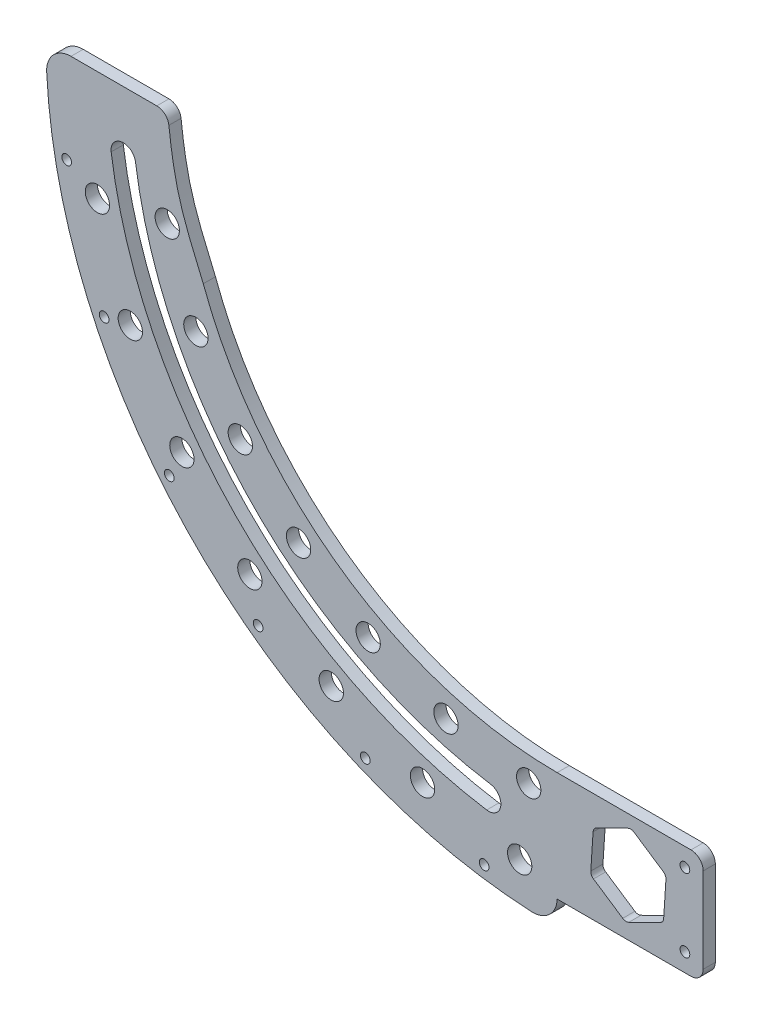
SolidWorks part; units mm, degrees
ref_plane "Front Plane" through (0, 0, 0) normal (0, 0, 1) x (1, 0, 0)
ref_plane "Top Plane" through (0, 0, 0) normal (0, 1, 0) x (1, 0, 0)
ref_plane "Right Plane" through (0, 0, 0) normal (1, 0, 0) x (0, 0, -1)
sketch "Layout" plane through (0, 0, 0) normal (0, 0, 1) x (1, 0, 0)
  line L0 (0, 0) -> (-76.2, 0) construction
  line L1 (-76.2, 0) -> (-203.2, 0) construction
  line L2 (-203.2, 0) -> (-254, 0) construction
  dimension "D1" = 76.2
  dimension "D2" = 127
  dimension "D3" = 50.8
sketch "Sketch1" plane through (0, 0, 0) normal (0, 0, 1) x (1, 0, 0)
  line L0 (0, 0) -> (-203.2, 0) construction
  line L1 (0, 0) -> (0, -203.2) construction
  line L2 (0, -203.2) -> (76.2, -203.2)
  line L3 (0, -254) -> (76.2, -254)
  line L4 (-254, 0) -> (-203.2, 0)
  line L5 (76.2, -203.2) -> (76.2, -254)
  arc A0 (-203.2, 0) -> (0, -203.2) centre (0, 0) ccw
  arc A1 (-254, 0) -> (0, -254) centre (0, 0) ccw
  dimension "D1" = 50.8
  dimension "D2" = 76.2
  dimension "D3" = 203.2
extrude "Boss-Extrude1" add sketch "Sketch1" along normal blind 6.35
ref_plane "Mid_Plane" through (0, 0, 3.175) normal (0, 0, 1) x (1, 0, 0)
sketch "Sketch2" plane through (0, 0, 6.35) normal (0, 0, 1) x (1, 0, 0)
  line L0 (0, 0) -> (-229.3095, 0) construction
  line L1 (0, 0) -> (-226.3753, -31.815) construction
  line L2 (0, 0) -> (-35.7609, -225.7856) construction
  arc A0 (-226.3753, -31.815) -> (-35.7609, -225.7856) centre (0, 0) ccw construction
  arc A1 (-226.3753, -31.815) -> (-35.7609, -225.7856) centre (0, 0) ccw construction
  arc A2 (-232.7264, -32.7076) -> (-36.7642, -232.1201) centre (0, 0) ccw
  arc A3 (-220.0242, -30.9224) -> (-34.7576, -219.451) centre (0, 0) ccw
  arc A4 (-220.0242, -30.9224) -> (-232.7264, -32.7076) centre (-226.3753, -31.815) ccw
  arc A5 (-36.7642, -232.1201) -> (-34.7576, -219.451) centre (-35.7609, -225.7856) ccw
  point P5 (-163.0491, -160.2279)
  dimension "D1" = 73
  dimension "D3" = 12.827
  dimension "D4" = 228.6
  dimension "D2" = 8
extrude "Cut-Extrude1" cut sketch "Sketch2" against normal up to next
fillet "Fillet1" [suppressed] radius 12.7
ref_point "Mid_Point"
sketch "Sketch4" plane through (0, 0, 0) normal (0, 0, -1) x (-1, 0, 0)
  line L0 (254, 0) -> (266.7, 0)
  line L1 (0, -254) -> (0, -266.7)
  arc A0 (0, -254) -> (254, 0) centre (0, 0) ccw construction
  arc A1 (0, -254) -> (254, 0) centre (0, 0) ccw
  arc A2 (0, -266.7) -> (266.7, 0) centre (0, 0) ccw
extrude "Boss-Extrude3" add sketch "Sketch4" against normal up to surface (6.35 mm away) up to face at (-145.6981, -143.1771, 6.35)
fillet "Fillet2" radius 12.7 2 edges at (-266.7, 0, 3.175) (0, -266.7, 3.175)
sketch "Sketch5" plane through (0, 0, 0) normal (0, 0, -1) x (-1, 0, 0)
  line L0 (2.758, -261.6055) -> (3.6103, -266.6756)
  line L1 (0, 0) -> (306.4939, -16.1536) construction
  line L2 (0, -261.62) -> (0.7987, -266.6988)
  line L3 (0, -261.62) -> (-1.3603, -266.6965)
  line L4 (2.758, -261.6055) -> (1.4514, -266.6961)
  line L5 (5.5157, -261.5618) -> (6.4214, -266.6227)
  line L6 (5.5157, -261.5618) -> (4.2628, -266.6659)
  line L7 (8.2728, -261.4892) -> (9.2318, -266.5402)
  line L8 (8.2728, -261.4892) -> (7.0738, -266.6062)
  line L9 (11.029, -261.3874) -> (12.0411, -266.428)
  line L10 (11.029, -261.3874) -> (9.884, -266.5168)
  line L11 (13.7839, -261.2566) -> (14.8492, -266.2863)
  line L12 (13.7839, -261.2566) -> (12.693, -266.3978)
  line L13 (16.5374, -261.0968) -> (17.6555, -266.115)
  line L14 (16.5374, -261.0968) -> (15.5007, -266.2492)
  line L15 (19.2889, -260.908) -> (20.46, -265.914)
  line L16 (19.2889, -260.908) -> (18.3067, -266.071)
  line L17 (22.0384, -260.6901) -> (23.2621, -265.6836)
  line L18 (22.0384, -260.6901) -> (21.1106, -265.8632)
  line L19 (24.7854, -260.4433) -> (26.0617, -265.4236)
  line L20 (24.7854, -260.4433) -> (23.9122, -265.6259)
  line L21 (27.5296, -260.1675) -> (28.8583, -265.1341)
  line L22 (27.5296, -260.1675) -> (26.7111, -265.359)
  line L23 (30.2708, -259.8629) -> (31.6518, -264.8151)
  line L24 (30.2708, -259.8629) -> (29.507, -265.0627)
  line L25 (33.0086, -259.5293) -> (34.4417, -264.4667)
  line L26 (33.0086, -259.5293) -> (32.2997, -264.7369)
  line L27 (35.7427, -259.1669) -> (37.2278, -264.089)
  line L28 (35.7427, -259.1669) -> (35.0888, -264.3817)
  line L29 (38.4729, -258.7757) -> (40.0098, -263.6818)
  line L30 (38.4729, -258.7757) -> (37.874, -263.9971)
  line L31 (41.1988, -258.3557) -> (42.7873, -263.2454)
  line L32 (41.1988, -258.3557) -> (40.6549, -263.5831)
  line L33 (43.9201, -257.9071) -> (45.5601, -262.7797)
  line L34 (43.9201, -257.9071) -> (43.4314, -263.1399)
  line L35 (46.6365, -257.4297) -> (48.3278, -262.2848)
  line L36 (46.6365, -257.4297) -> (46.203, -262.6674)
  line L37 (49.3478, -256.9238) -> (51.0902, -261.7607)
  line L38 (49.3478, -256.9238) -> (48.9695, -262.1657)
  line L39 (52.0535, -256.3893) -> (53.8468, -261.2076)
  line L40 (52.0535, -256.3893) -> (51.7305, -261.6349)
  line L41 (54.7535, -255.8263) -> (56.5975, -260.6254)
  line L42 (54.7535, -255.8263) -> (54.4858, -261.0751)
  line L43 (57.4474, -255.2348) -> (59.3419, -260.0143)
  line L44 (57.4474, -255.2348) -> (57.2351, -260.4862)
  line L45 (60.1349, -254.615) -> (62.0797, -259.3743)
  line L46 (60.1349, -254.615) -> (59.978, -259.8683)
  line L47 (62.8157, -253.9669) -> (64.8106, -258.7054)
  line L48 (62.8157, -253.9669) -> (62.7142, -259.2216)
  line L49 (65.4896, -253.2906) -> (67.5342, -258.0078)
  line L50 (65.4896, -253.2906) -> (65.4434, -258.546)
  line L51 (68.1561, -252.5862) -> (70.2504, -257.2815)
  line L52 (68.1561, -252.5862) -> (68.1654, -257.8418)
  line L53 (70.8151, -251.8536) -> (72.9588, -256.5266)
  line L54 (70.8151, -251.8536) -> (70.8798, -257.1088)
  line L55 (73.4663, -251.0931) -> (75.6591, -255.7432)
  line L56 (73.4663, -251.0931) -> (73.5863, -256.3473)
  line L57 (76.1092, -250.3046) -> (78.3509, -254.9314)
  line L58 (76.1092, -250.3046) -> (76.2846, -255.5573)
  line L59 (78.7437, -249.4884) -> (81.0341, -254.0913)
  line L60 (78.7437, -249.4884) -> (78.9745, -254.7389)
  line L61 (81.3695, -248.6444) -> (83.7082, -253.2229)
  line L62 (81.3695, -248.6444) -> (81.6556, -253.8922)
  line L63 (83.9862, -247.7728) -> (86.373, -252.3263)
  line L64 (83.9862, -247.7728) -> (84.3276, -253.0173)
  line L65 (86.5935, -246.8736) -> (89.0283, -251.4018)
  line L66 (86.5935, -246.8736) -> (86.9902, -252.1142)
  line L67 (89.1913, -245.947) -> (91.6736, -250.4493)
  line L68 (89.1913, -245.947) -> (89.6432, -251.1832)
  line L69 (91.7791, -244.9931) -> (94.3088, -249.4689)
  line L70 (91.7791, -244.9931) -> (92.2862, -250.2242)
  line L71 (94.3567, -244.0119) -> (96.9335, -248.4608)
  line L72 (94.3567, -244.0119) -> (94.919, -249.2374)
  line L73 (96.9239, -243.0037) -> (99.5474, -247.4252)
  line L74 (96.9239, -243.0037) -> (97.5412, -248.2229)
  line L75 (99.4803, -241.9684) -> (102.1502, -246.362)
  line L76 (99.4803, -241.9684) -> (100.1525, -247.1808)
  line L77 (102.0256, -240.9062) -> (104.7417, -245.2714)
  line L78 (102.0256, -240.9062) -> (102.7528, -246.1113)
  line L79 (104.5596, -239.8173) -> (107.3215, -244.1536)
  line L80 (104.5596, -239.8173) -> (105.3416, -245.0144)
  line L81 (107.0819, -238.7017) -> (109.8895, -243.0086)
  line L82 (107.0819, -238.7017) -> (107.9187, -243.8902)
  line L83 (109.5924, -237.5595) -> (112.4452, -241.8367)
  line L84 (109.5924, -237.5595) -> (110.4838, -242.739)
  line L85 (112.0907, -236.391) -> (114.9884, -240.6378)
  line L86 (112.0907, -236.391) -> (113.0366, -241.5608)
  line L87 (114.5765, -235.1962) -> (117.5188, -239.4122)
  line L88 (114.5765, -235.1962) -> (115.5769, -240.3557)
  line L89 (117.0496, -233.9753) -> (120.0362, -238.16)
  line L90 (117.0496, -233.9753) -> (118.1043, -239.124)
  line L91 (119.5096, -232.7283) -> (122.5402, -236.8814)
  line L92 (119.5096, -232.7283) -> (120.6186, -237.8656)
  line L93 (121.9564, -231.4555) -> (125.0306, -235.5764)
  line L94 (121.9564, -231.4555) -> (123.1195, -236.5808)
  line L95 (124.3897, -230.157) -> (127.5071, -234.2452)
  line L96 (124.3897, -230.157) -> (125.6067, -235.2697)
  line L97 (126.8091, -228.8329) -> (129.9695, -232.888)
  line L98 (126.8091, -228.8329) -> (128.0799, -233.9325)
  line L99 (129.2144, -227.4833) -> (132.4174, -231.5049)
  line L100 (129.2144, -227.4833) -> (130.539, -232.5693)
  line L101 (131.6054, -226.1085) -> (134.8505, -230.0961)
  line L102 (131.6054, -226.1085) -> (132.9835, -231.1802)
  line L103 (133.9817, -224.7085) -> (137.2687, -228.6617)
  line L104 (133.9817, -224.7085) -> (135.4132, -229.7654)
  line L105 (136.3432, -223.2836) -> (139.6717, -227.2019)
  line L106 (136.3432, -223.2836) -> (137.8279, -228.3251)
  line L107 (138.6895, -221.8339) -> (142.0591, -225.7169)
  line L108 (138.6895, -221.8339) -> (140.2272, -226.8595)
  line L109 (141.0203, -220.3595) -> (144.4307, -224.2067)
  line L110 (141.0203, -220.3595) -> (142.611, -225.3686)
  line L111 (143.3355, -218.8606) -> (146.7863, -222.6717)
  line L112 (143.3355, -218.8606) -> (144.9789, -223.8526)
  line L113 (145.6348, -217.3374) -> (149.1256, -221.1119)
  line L114 (145.6348, -217.3374) -> (147.3307, -222.3118)
  line L115 (147.9179, -215.79) -> (151.4482, -219.5275)
  line L116 (147.9179, -215.79) -> (149.6662, -220.7463)
  line L117 (150.1846, -214.2186) -> (153.7541, -217.9187)
  line L118 (150.1846, -214.2186) -> (151.985, -219.1562)
  line L119 (152.4345, -212.6235) -> (156.0429, -216.2857)
  line L120 (152.4345, -212.6235) -> (154.2869, -217.5418)
  line L121 (154.6675, -211.0047) -> (158.3143, -214.6287)
  line L122 (154.6675, -211.0047) -> (156.5717, -215.9032)
  line L123 (156.8834, -209.3624) -> (160.5681, -212.9478)
  line L124 (156.8834, -209.3624) -> (158.839, -214.2407)
  line L125 (159.0818, -207.6969) -> (162.8041, -211.2432)
  line L126 (159.0818, -207.6969) -> (161.0887, -212.5543)
  line L127 (161.2625, -206.0083) -> (165.022, -209.5152)
  line L128 (161.2625, -206.0083) -> (163.3205, -210.8442)
  line L129 (163.4253, -204.2969) -> (167.2216, -207.7639)
  line L130 (163.4253, -204.2969) -> (165.5342, -209.1108)
  line L131 (165.5699, -202.5627) -> (169.4025, -205.9895)
  line L132 (165.5699, -202.5627) -> (167.7295, -207.3541)
  line L133 (167.6961, -200.806) -> (171.5647, -204.1922)
  line L134 (167.6961, -200.806) -> (169.9061, -205.5744)
  line L135 (169.8037, -199.0269) -> (173.7077, -202.3722)
  line L136 (169.8037, -199.0269) -> (172.0638, -203.7718)
  line L137 (171.8924, -197.2258) -> (175.8315, -200.5297)
  line L138 (171.8924, -197.2258) -> (174.2024, -201.9465)
  line L139 (173.962, -195.4027) -> (177.9357, -198.665)
  line L140 (173.962, -195.4027) -> (176.3217, -200.0989)
  line L141 (176.0123, -193.558) -> (180.0202, -196.7781)
  line L142 (176.0123, -193.558) -> (178.4213, -198.229)
  line L143 (178.043, -191.6917) -> (182.0846, -194.8694)
  line L144 (178.043, -191.6917) -> (180.5012, -196.337)
  line L145 (180.054, -189.8041) -> (184.1288, -192.939)
  line L146 (180.054, -189.8041) -> (182.5609, -194.4232)
  line L147 (182.0449, -187.8954) -> (186.1526, -190.9872)
  line L148 (182.0449, -187.8954) -> (184.6004, -192.4879)
  line L149 (184.0156, -185.9658) -> (188.1556, -189.0141)
  line L150 (184.0156, -185.9658) -> (186.6194, -190.5311)
  line L151 (185.9658, -184.0156) -> (190.1378, -187.0201)
  line L152 (185.9658, -184.0156) -> (188.6176, -188.5532)
  line L153 (187.8954, -182.0449) -> (192.0988, -185.0053)
  line L154 (187.8954, -182.0449) -> (190.5948, -186.5543)
  line L155 (189.8041, -180.054) -> (194.0384, -182.9699)
  line L156 (189.8041, -180.054) -> (192.5509, -184.5346)
  line L157 (191.6917, -178.043) -> (195.9565, -180.9141)
  line L158 (191.6917, -178.043) -> (194.4856, -182.4945)
  line L159 (193.558, -176.0123) -> (197.8529, -178.8383)
  line L160 (193.558, -176.0123) -> (196.3987, -180.4341)
  line L161 (195.4027, -173.962) -> (199.7272, -176.7426)
  line L162 (195.4027, -173.962) -> (198.2899, -178.3536)
  line L163 (197.2258, -171.8924) -> (201.5793, -174.6272)
  line L164 (197.2258, -171.8924) -> (200.1591, -176.2533)
  line L165 (199.0269, -169.8037) -> (203.4091, -172.4925)
  line L166 (199.0269, -169.8037) -> (202.006, -174.1334)
  line L167 (200.806, -167.6961) -> (205.2162, -170.3385)
  line L168 (200.806, -167.6961) -> (203.8305, -171.9942)
  line L169 (202.5627, -165.5699) -> (207.0005, -168.1656)
  line L170 (202.5627, -165.5699) -> (205.6324, -169.8358)
  line L171 (204.2969, -163.4253) -> (208.7618, -165.9741)
  line L172 (204.2969, -163.4253) -> (207.4114, -167.6586)
  line L173 (206.0083, -161.2625) -> (210.4999, -163.7641)
  line L174 (206.0083, -161.2625) -> (209.1673, -165.4628)
  line L175 (207.6969, -159.0818) -> (212.2146, -161.5359)
  line L176 (207.6969, -159.0818) -> (210.9, -163.2485)
  line L177 (209.3624, -156.8834) -> (213.9058, -159.2897)
  line L178 (209.3624, -156.8834) -> (212.6093, -161.0161)
  line L179 (211.0047, -154.6675) -> (215.5731, -157.0259)
  line L180 (211.0047, -154.6675) -> (214.2949, -158.7658)
  line L181 (212.6235, -152.4345) -> (217.2165, -154.7446)
  line L182 (212.6235, -152.4345) -> (215.9567, -156.4979)
  line L183 (214.2186, -150.1846) -> (218.8358, -152.446)
  line L184 (214.2186, -150.1846) -> (217.5945, -154.2126)
  line L185 (215.79, -147.9179) -> (220.4307, -150.1306)
  line L186 (215.79, -147.9179) -> (219.2081, -151.9101)
  line L187 (217.3374, -145.6348) -> (222.0011, -147.7985)
  line L188 (217.3374, -145.6348) -> (220.7974, -149.5908)
  line L189 (218.8606, -143.3355) -> (223.5469, -145.4499)
  line L190 (218.8606, -143.3355) -> (222.3621, -147.2548)
  line L191 (220.3595, -141.0203) -> (225.0678, -143.0852)
  line L192 (220.3595, -141.0203) -> (223.9021, -144.9024)
  line L193 (221.8339, -138.6895) -> (226.5637, -140.7045)
  line L194 (221.8339, -138.6895) -> (225.4173, -142.534)
  line L195 (223.2836, -136.3432) -> (228.0345, -138.3083)
  line L196 (223.2836, -136.3432) -> (226.9074, -140.1497)
  line L197 (224.7085, -133.9817) -> (229.4798, -135.8966)
  line L198 (224.7085, -133.9817) -> (228.3722, -137.7499)
  line L199 (226.1085, -131.6054) -> (230.8997, -133.4699)
  line L200 (226.1085, -131.6054) -> (229.8117, -135.3347)
  line L201 (227.4833, -129.2144) -> (232.2939, -131.0283)
  line L202 (227.4833, -129.2144) -> (231.2256, -132.9045)
  line L203 (228.8329, -126.8091) -> (233.6623, -128.5722)
  line L204 (228.8329, -126.8091) -> (232.6139, -130.4595)
  line L205 (230.157, -124.3897) -> (235.0048, -126.1017)
  line L206 (230.157, -124.3897) -> (233.9762, -128)
  line L207 (231.4555, -121.9564) -> (236.3211, -123.6173)
  line L208 (231.4555, -121.9564) -> (235.3126, -125.5263)
  line L209 (232.7283, -119.5096) -> (237.6111, -121.1191)
  line L210 (232.7283, -119.5096) -> (236.6229, -123.0387)
  line L211 (233.9753, -117.0496) -> (238.8748, -118.6075)
  line L212 (233.9753, -117.0496) -> (237.9068, -120.5373)
  line L213 (235.1962, -114.5765) -> (240.1119, -116.0827)
  line L214 (235.1962, -114.5765) -> (239.1643, -118.0226)
  line L215 (236.391, -112.0907) -> (241.3223, -113.5449)
  line L216 (236.391, -112.0907) -> (240.3952, -115.4948)
  line L217 (237.5595, -109.5924) -> (242.5059, -110.9946)
  line L218 (237.5595, -109.5924) -> (241.5994, -112.9541)
  line L219 (238.7017, -107.0819) -> (243.6625, -108.4319)
  line L220 (238.7017, -107.0819) -> (242.7767, -110.4009)
  line L221 (239.8173, -104.5596) -> (244.792, -105.8572)
  line L222 (239.8173, -104.5596) -> (243.9271, -107.8353)
  line L223 (240.9062, -102.0256) -> (245.8944, -103.2707)
  line L224 (240.9062, -102.0256) -> (245.0503, -105.2579)
  line L225 (241.9684, -99.4803) -> (246.9694, -100.6727)
  line L226 (241.9684, -99.4803) -> (246.1464, -102.6687)
  line L227 (243.0037, -96.9239) -> (248.017, -98.0636)
  line L228 (243.0037, -96.9239) -> (247.215, -100.0681)
  line L229 (244.0119, -94.3567) -> (249.037, -95.4435)
  line L230 (244.0119, -94.3567) -> (248.2562, -97.4564)
  line L231 (244.9931, -91.7791) -> (250.0293, -92.8128)
  line L232 (244.9931, -91.7791) -> (249.2698, -94.8338)
  line L233 (245.947, -89.1913) -> (250.9939, -90.1718)
  line L234 (245.947, -89.1913) -> (250.2557, -92.2007)
  line L235 (246.8736, -86.5935) -> (251.9305, -87.5208)
  line L236 (246.8736, -86.5935) -> (251.2138, -89.5574)
  line L237 (247.7728, -83.9862) -> (252.8392, -84.8601)
  line L238 (247.7728, -83.9862) -> (252.1439, -86.9041)
  line L239 (248.6444, -81.3695) -> (253.7197, -82.1899)
  line L240 (248.6444, -81.3695) -> (253.0461, -84.2412)
  line L241 (249.4884, -78.7437) -> (254.5721, -79.5107)
  line L242 (249.4884, -78.7437) -> (253.9201, -81.5689)
  line L243 (250.3046, -76.1092) -> (255.3961, -76.8225)
  line L244 (250.3046, -76.1092) -> (254.7659, -78.8875)
  line L245 (251.0931, -73.4663) -> (256.1918, -74.1258)
  line L246 (251.0931, -73.4663) -> (255.5834, -76.1973)
  line L247 (251.8536, -70.8151) -> (256.959, -71.4209)
  line L248 (251.8536, -70.8151) -> (256.3724, -73.4987)
  line L249 (252.5862, -68.1561) -> (257.6977, -68.7081)
  line L250 (252.5862, -68.1561) -> (257.133, -70.7919)
  line L251 (253.2906, -65.4896) -> (258.4077, -65.9876)
  line L252 (253.2906, -65.4896) -> (257.865, -68.0773)
  line L253 (253.9669, -62.8157) -> (259.089, -63.2598)
  line L254 (253.9669, -62.8157) -> (258.5684, -65.3551)
  line L255 (254.615, -60.1349) -> (259.7415, -60.5249)
  line L256 (254.615, -60.1349) -> (259.243, -62.6256)
  line L257 (255.2348, -57.4474) -> (260.3651, -57.7834)
  line L258 (255.2348, -57.4474) -> (259.8888, -59.8892)
  line L259 (255.8263, -54.7535) -> (260.9598, -55.0354)
  line L260 (255.8263, -54.7535) -> (260.5057, -57.1461)
  line L261 (256.3893, -52.0535) -> (261.5254, -52.2813)
  line L262 (256.3893, -52.0535) -> (261.0937, -54.3966)
  line L263 (256.9238, -49.3478) -> (262.0621, -49.5213)
  line L264 (256.9238, -49.3478) -> (261.6526, -51.6412)
  line L265 (257.4297, -46.6365) -> (262.5696, -46.7559)
  line L266 (257.4297, -46.6365) -> (262.1825, -48.8799)
  line L267 (257.9071, -43.9201) -> (263.0479, -43.9853)
  line L268 (257.9071, -43.9201) -> (262.6832, -46.1133)
  line L269 (258.3557, -41.1988) -> (263.497, -41.2098)
  line L270 (258.3557, -41.1988) -> (263.1547, -43.3415)
  line L271 (258.7757, -38.4729) -> (263.9167, -38.4297)
  line L272 (258.7757, -38.4729) -> (263.597, -40.5649)
  line L273 (259.1669, -35.7427) -> (264.3072, -35.6453)
  line L274 (259.1669, -35.7427) -> (264.01, -37.7838)
  line L275 (259.5293, -33.0086) -> (264.6683, -32.857)
  line L276 (259.5293, -33.0086) -> (264.3936, -34.9985)
  line L277 (259.8629, -30.2708) -> (265, -30.065)
  line L278 (259.8629, -30.2708) -> (264.7479, -32.2093)
  line L279 (260.1675, -27.5296) -> (265.3022, -27.2697)
  line L280 (260.1675, -27.5296) -> (265.0727, -29.4165)
  line L281 (260.4433, -24.7854) -> (265.5749, -24.4714)
  line L282 (260.4433, -24.7854) -> (265.3681, -26.6204)
  line L283 (260.6901, -22.0384) -> (265.8181, -21.6703)
  line L284 (260.6901, -22.0384) -> (265.634, -23.8214)
  line L285 (260.908, -19.2889) -> (266.0318, -18.8668)
  line L286 (260.908, -19.2889) -> (265.8704, -21.0198)
  line L287 (261.0968, -16.5374) -> (266.2159, -16.0612)
  line L288 (261.0968, -16.5374) -> (266.0772, -18.2158)
  line L289 (261.2566, -13.7839) -> (266.3705, -13.2539)
  line L290 (261.2566, -13.7839) -> (266.2544, -15.4098)
  line L291 (261.3874, -11.029) -> (266.4954, -10.4451)
  line L292 (261.3874, -11.029) -> (266.4021, -12.602)
  line L301 (0, 0) -> (0, -261.62) construction
  arc A0 (13.3308, -266.3666) -> (266.3664, -13.335) centre (0, 0) ccw construction
  arc A1 (-1.3603, -266.6965) -> (0.7987, -266.6988) centre (0, 0) ccw
  arc A2 (1.4514, -266.6961) -> (3.6103, -266.6756) centre (0, 0) ccw
  arc A3 (4.2628, -266.6659) -> (6.4214, -266.6227) centre (0, 0) ccw
  arc A4 (7.0738, -266.6062) -> (9.2318, -266.5402) centre (0, 0) ccw
  arc A5 (9.884, -266.5168) -> (12.0411, -266.428) centre (0, 0) ccw
  arc A6 (12.693, -266.3978) -> (14.8492, -266.2863) centre (0, 0) ccw
  arc A7 (15.5007, -266.2492) -> (17.6555, -266.115) centre (0, 0) ccw
  arc A8 (18.3067, -266.071) -> (20.46, -265.914) centre (0, 0) ccw
  arc A9 (21.1106, -265.8632) -> (23.2621, -265.6836) centre (0, 0) ccw
  arc A10 (23.9122, -265.6259) -> (26.0617, -265.4236) centre (0, 0) ccw
  arc A11 (26.7111, -265.359) -> (28.8583, -265.1341) centre (0, 0) ccw
  arc A12 (29.507, -265.0627) -> (31.6518, -264.8151) centre (0, 0) ccw
  arc A13 (32.2997, -264.7369) -> (34.4417, -264.4667) centre (0, 0) ccw
  arc A14 (35.0888, -264.3817) -> (37.2278, -264.089) centre (0, 0) ccw
  arc A15 (37.874, -263.9971) -> (40.0098, -263.6818) centre (0, 0) ccw
  arc A16 (40.6549, -263.5831) -> (42.7873, -263.2454) centre (0, 0) ccw
  arc A17 (43.4314, -263.1399) -> (45.5601, -262.7797) centre (0, 0) ccw
  arc A18 (46.203, -262.6674) -> (48.3278, -262.2848) centre (0, 0) ccw
  arc A19 (48.9695, -262.1657) -> (51.0902, -261.7607) centre (0, 0) ccw
  arc A20 (51.7305, -261.6349) -> (53.8468, -261.2076) centre (0, 0) ccw
  arc A21 (54.4858, -261.0751) -> (56.5975, -260.6254) centre (0, 0) ccw
  arc A22 (57.2351, -260.4862) -> (59.3419, -260.0143) centre (0, 0) ccw
  arc A23 (59.978, -259.8683) -> (62.0797, -259.3743) centre (0, 0) ccw
  arc A24 (62.7142, -259.2216) -> (64.8106, -258.7054) centre (0, 0) ccw
  arc A25 (65.4434, -258.546) -> (67.5342, -258.0078) centre (0, 0) ccw
  arc A26 (68.1654, -257.8418) -> (70.2504, -257.2815) centre (0, 0) ccw
  arc A27 (70.8798, -257.1088) -> (72.9588, -256.5266) centre (0, 0) ccw
  arc A28 (73.5863, -256.3473) -> (75.6591, -255.7432) centre (0, 0) ccw
  arc A29 (76.2846, -255.5573) -> (78.3509, -254.9314) centre (0, 0) ccw
  arc A30 (78.9745, -254.7389) -> (81.0341, -254.0913) centre (0, 0) ccw
  arc A31 (81.6556, -253.8922) -> (83.7082, -253.2229) centre (0, 0) ccw
  arc A32 (84.3276, -253.0173) -> (86.373, -252.3263) centre (0, 0) ccw
  arc A33 (86.9902, -252.1142) -> (89.0283, -251.4018) centre (0, 0) ccw
  arc A34 (89.6432, -251.1832) -> (91.6736, -250.4493) centre (0, 0) ccw
  arc A35 (92.2862, -250.2242) -> (94.3088, -249.4689) centre (0, 0) ccw
  arc A36 (94.919, -249.2374) -> (96.9335, -248.4608) centre (0, 0) ccw
  arc A37 (97.5412, -248.2229) -> (99.5474, -247.4252) centre (0, 0) ccw
  arc A38 (100.1525, -247.1808) -> (102.1502, -246.362) centre (0, 0) ccw
  arc A39 (102.7528, -246.1113) -> (104.7417, -245.2714) centre (0, 0) ccw
  arc A40 (105.3416, -245.0144) -> (107.3215, -244.1536) centre (0, 0) ccw
  arc A41 (107.9187, -243.8902) -> (109.8895, -243.0086) centre (0, 0) ccw
  arc A42 (110.4838, -242.739) -> (112.4452, -241.8367) centre (0, 0) ccw
  arc A43 (113.0366, -241.5608) -> (114.9884, -240.6378) centre (0, 0) ccw
  arc A44 (115.5769, -240.3557) -> (117.5188, -239.4122) centre (0, 0) ccw
  arc A45 (118.1043, -239.124) -> (120.0362, -238.16) centre (0, 0) ccw
  arc A46 (120.6186, -237.8656) -> (122.5402, -236.8814) centre (0, 0) ccw
  arc A47 (123.1195, -236.5808) -> (125.0306, -235.5764) centre (0, 0) ccw
  arc A48 (125.6067, -235.2697) -> (127.5071, -234.2452) centre (0, 0) ccw
  arc A49 (128.0799, -233.9325) -> (129.9695, -232.888) centre (0, 0) ccw
  arc A50 (130.539, -232.5693) -> (132.4174, -231.5049) centre (0, 0) ccw
  arc A51 (132.9835, -231.1802) -> (134.8505, -230.0961) centre (0, 0) ccw
  arc A52 (135.4132, -229.7654) -> (137.2687, -228.6617) centre (0, 0) ccw
  arc A53 (137.8279, -228.3251) -> (139.6717, -227.2019) centre (0, 0) ccw
  arc A54 (140.2272, -226.8595) -> (142.0591, -225.7169) centre (0, 0) ccw
  arc A55 (142.611, -225.3686) -> (144.4307, -224.2067) centre (0, 0) ccw
  arc A56 (144.9789, -223.8526) -> (146.7863, -222.6717) centre (0, 0) ccw
  arc A57 (147.3307, -222.3118) -> (149.1256, -221.1119) centre (0, 0) ccw
  arc A58 (149.6662, -220.7463) -> (151.4482, -219.5275) centre (0, 0) ccw
  arc A59 (151.985, -219.1562) -> (153.7541, -217.9187) centre (0, 0) ccw
  arc A60 (154.2869, -217.5418) -> (156.0429, -216.2857) centre (0, 0) ccw
  arc A61 (156.5717, -215.9032) -> (158.3143, -214.6287) centre (0, 0) ccw
  arc A62 (158.839, -214.2407) -> (160.5681, -212.9478) centre (0, 0) ccw
  arc A63 (161.0887, -212.5543) -> (162.8041, -211.2432) centre (0, 0) ccw
  arc A64 (163.3205, -210.8442) -> (165.022, -209.5152) centre (0, 0) ccw
  arc A65 (165.5342, -209.1108) -> (167.2216, -207.7639) centre (0, 0) ccw
  arc A66 (167.7295, -207.3541) -> (169.4025, -205.9895) centre (0, 0) ccw
  arc A67 (169.9061, -205.5744) -> (171.5647, -204.1922) centre (0, 0) ccw
  arc A68 (172.0638, -203.7718) -> (173.7077, -202.3722) centre (0, 0) ccw
  arc A69 (174.2024, -201.9465) -> (175.8315, -200.5297) centre (0, 0) ccw
  arc A70 (176.3217, -200.0989) -> (177.9357, -198.665) centre (0, 0) ccw
  arc A71 (178.4213, -198.229) -> (180.0202, -196.7781) centre (0, 0) ccw
  arc A72 (180.5012, -196.337) -> (182.0846, -194.8694) centre (0, 0) ccw
  arc A73 (182.5609, -194.4232) -> (184.1288, -192.939) centre (0, 0) ccw
  arc A74 (184.6004, -192.4879) -> (186.1526, -190.9872) centre (0, 0) ccw
  arc A75 (186.6194, -190.5311) -> (188.1556, -189.0141) centre (0, 0) ccw
  arc A76 (188.6176, -188.5532) -> (190.1378, -187.0201) centre (0, 0) ccw
  arc A77 (190.5948, -186.5543) -> (192.0988, -185.0053) centre (0, 0) ccw
  arc A78 (192.5509, -184.5346) -> (194.0384, -182.9699) centre (0, 0) ccw
  arc A79 (194.4856, -182.4945) -> (195.9565, -180.9141) centre (0, 0) ccw
  arc A80 (196.3987, -180.4341) -> (197.8529, -178.8383) centre (0, 0) ccw
  arc A81 (198.2899, -178.3536) -> (199.7272, -176.7426) centre (0, 0) ccw
  arc A82 (200.1591, -176.2533) -> (201.5793, -174.6272) centre (0, 0) ccw
  arc A83 (202.006, -174.1334) -> (203.4091, -172.4925) centre (0, 0) ccw
  arc A84 (203.8305, -171.9942) -> (205.2162, -170.3385) centre (0, 0) ccw
  arc A85 (205.6324, -169.8358) -> (207.0005, -168.1656) centre (0, 0) ccw
  arc A86 (207.4114, -167.6586) -> (208.7618, -165.9741) centre (0, 0) ccw
  arc A87 (209.1673, -165.4628) -> (210.4999, -163.7641) centre (0, 0) ccw
  arc A88 (210.9, -163.2485) -> (212.2146, -161.5359) centre (0, 0) ccw
  arc A89 (212.6093, -161.0161) -> (213.9058, -159.2897) centre (0, 0) ccw
  arc A90 (214.2949, -158.7658) -> (215.5731, -157.0259) centre (0, 0) ccw
  arc A91 (215.9567, -156.4979) -> (217.2165, -154.7446) centre (0, 0) ccw
  arc A92 (217.5945, -154.2126) -> (218.8358, -152.446) centre (0, 0) ccw
  arc A93 (219.2081, -151.9101) -> (220.4307, -150.1306) centre (0, 0) ccw
  arc A94 (220.7974, -149.5908) -> (222.0011, -147.7985) centre (0, 0) ccw
  arc A95 (222.3621, -147.2548) -> (223.5469, -145.4499) centre (0, 0) ccw
  arc A96 (223.9021, -144.9024) -> (225.0678, -143.0852) centre (0, 0) ccw
  arc A97 (225.4173, -142.534) -> (226.5637, -140.7045) centre (0, 0) ccw
  arc A98 (226.9074, -140.1497) -> (228.0345, -138.3083) centre (0, 0) ccw
  arc A99 (228.3722, -137.7499) -> (229.4798, -135.8966) centre (0, 0) ccw
  arc A100 (229.8117, -135.3347) -> (230.8997, -133.4699) centre (0, 0) ccw
  arc A101 (231.2256, -132.9045) -> (232.2939, -131.0283) centre (0, 0) ccw
  arc A102 (232.6139, -130.4595) -> (233.6623, -128.5722) centre (0, 0) ccw
  arc A103 (233.9762, -128) -> (235.0048, -126.1017) centre (0, 0) ccw
  arc A104 (235.3126, -125.5263) -> (236.3211, -123.6173) centre (0, 0) ccw
  arc A105 (236.6229, -123.0387) -> (237.6111, -121.1191) centre (0, 0) ccw
  arc A106 (237.9068, -120.5373) -> (238.8748, -118.6075) centre (0, 0) ccw
  arc A107 (239.1643, -118.0226) -> (240.1119, -116.0827) centre (0, 0) ccw
  arc A108 (240.3952, -115.4948) -> (241.3223, -113.5449) centre (0, 0) ccw
  arc A109 (241.5994, -112.9541) -> (242.5059, -110.9946) centre (0, 0) ccw
  arc A110 (242.7767, -110.4009) -> (243.6625, -108.4319) centre (0, 0) ccw
  arc A111 (243.9271, -107.8353) -> (244.792, -105.8572) centre (0, 0) ccw
  arc A112 (245.0503, -105.2579) -> (245.8944, -103.2707) centre (0, 0) ccw
  arc A113 (246.1464, -102.6687) -> (246.9694, -100.6727) centre (0, 0) ccw
  arc A114 (247.215, -100.0681) -> (248.017, -98.0636) centre (0, 0) ccw
  arc A115 (248.2562, -97.4564) -> (249.037, -95.4435) centre (0, 0) ccw
  arc A116 (249.2698, -94.8338) -> (250.0293, -92.8128) centre (0, 0) ccw
  arc A117 (250.2557, -92.2007) -> (250.9939, -90.1718) centre (0, 0) ccw
  arc A118 (251.2138, -89.5574) -> (251.9305, -87.5208) centre (0, 0) ccw
  arc A119 (252.1439, -86.9041) -> (252.8392, -84.8601) centre (0, 0) ccw
  arc A120 (253.0461, -84.2412) -> (253.7197, -82.1899) centre (0, 0) ccw
  arc A121 (253.9201, -81.5689) -> (254.5721, -79.5107) centre (0, 0) ccw
  arc A122 (254.7659, -78.8875) -> (255.3961, -76.8225) centre (0, 0) ccw
  arc A123 (255.5834, -76.1973) -> (256.1918, -74.1258) centre (0, 0) ccw
  arc A124 (256.3724, -73.4987) -> (256.959, -71.4209) centre (0, 0) ccw
  arc A125 (257.133, -70.7919) -> (257.6977, -68.7081) centre (0, 0) ccw
  arc A126 (257.865, -68.0773) -> (258.4077, -65.9876) centre (0, 0) ccw
  arc A127 (258.5684, -65.3551) -> (259.089, -63.2598) centre (0, 0) ccw
  arc A128 (259.243, -62.6256) -> (259.7415, -60.5249) centre (0, 0) ccw
  arc A129 (259.8888, -59.8892) -> (260.3651, -57.7834) centre (0, 0) ccw
  arc A130 (260.5057, -57.1461) -> (260.9598, -55.0354) centre (0, 0) ccw
  arc A131 (261.0937, -54.3966) -> (261.5254, -52.2813) centre (0, 0) ccw
  arc A132 (261.6526, -51.6412) -> (262.0621, -49.5213) centre (0, 0) ccw
  arc A133 (262.1825, -48.8799) -> (262.5696, -46.7559) centre (0, 0) ccw
  arc A134 (262.6832, -46.1133) -> (263.0479, -43.9853) centre (0, 0) ccw
  arc A135 (263.1547, -43.3415) -> (263.497, -41.2098) centre (0, 0) ccw
  arc A136 (263.597, -40.5649) -> (263.9167, -38.4297) centre (0, 0) ccw
  arc A137 (264.01, -37.7838) -> (264.3072, -35.6453) centre (0, 0) ccw
  arc A138 (264.3936, -34.9985) -> (264.6683, -32.857) centre (0, 0) ccw
  arc A139 (264.7479, -32.2093) -> (265, -30.065) centre (0, 0) ccw
  arc A140 (265.0727, -29.4165) -> (265.3022, -27.2697) centre (0, 0) ccw
  arc A141 (265.3681, -26.6204) -> (265.5749, -24.4714) centre (0, 0) ccw
  arc A142 (265.634, -23.8214) -> (265.8181, -21.6703) centre (0, 0) ccw
  arc A143 (265.8704, -21.0198) -> (266.0318, -18.8668) centre (0, 0) ccw
  arc A144 (266.0772, -18.2158) -> (266.2159, -16.0612) centre (0, 0) ccw
  arc A145 (266.2544, -15.4098) -> (266.3705, -13.2539) centre (0, 0) ccw
  arc A146 (266.4021, -12.602) -> (266.4954, -10.4451) centre (0, 0) ccw
  dimension "D1" = 2.159
  dimension "D2" = 146
  dimension "D4" = 261.62
extrude "Cut-Extrude2" [suppressed] cut sketch "Sketch5" against normal up to surface (6.35 mm away) up to face at (-145.6981, -143.1771, 6.35)
sketch "Sketch6" plane through (0, 0, 6.35) normal (0, 0, 1) x (1, 0, 0)
  line L0 (0, 0) -> (-202.3753, -163.7976) construction
  circle A1 centre (-255.9253, -47.8297) radius 2.54
  circle A2 centre (-236.3726, -109.1487) radius 2.54
  circle A3 centre (-202.3753, -163.7976) radius 2.54
  circle A4 centre (-156.0111, -208.437) radius 2.54
  circle A5 centre (-100.1131, -240.3389) radius 2.54
  circle A6 centre (-38.0972, -257.5539) radius 2.54
  point P15 (0, 0)
  dimension "D1" = 6
extrude "Cut-Extrude3" cut sketch "Sketch6" against normal through all
sketch "Sketch9" plane through (0, 0, 6.35) normal (0, 0, 1) x (1, 0, 0)
  line L0 (76.2, -203.2) -> (0, -203.2) construction
  line L1 (76.2, -203.2) -> (0, -203.2)
  line L2 (76.2, -196.85) -> (0, -196.85)
  line L3 (76.2, -203.2) -> (76.2, -196.85)
  arc A1 (-203.2, 0) -> (0, -203.2) centre (0, 0) ccw construction
  arc A2 (-203.2, 0) -> (0, -203.2) centre (0, 0) ccw
  arc A3 (-184.643, -68.2412) -> (0, -196.85) centre (0, 0) ccw
  arc A4 (-196.85, 0) -> (0, -196.85) centre (0, 0) ccw construction
  spline S0 degree 3 poles (-203.2, 0) (-199.8847, -32.721) (-195.8268, -42.2466) (-184.643, -68.2412) knots 0 0 0 0 1 1 1 1
  dimension "D1" = 6.35
extrude "Boss-Extrude4" add sketch "Sketch9" against normal up to surface (6.35 mm away) up to face at (-233.8326, -109.1487, 0)
sketch "Sketch10" plane through (0, 0, 0) normal (0, 0, -1) x (-1, 0, 0)
  line L0 (0, 0) -> (14.8412, -209.1023) construction
  line L1 (0, 0) -> (57.9917, -201.4472) construction
  line L2 (0, 0) -> (19.5425, -245.8839) construction
  line L3 (0, 0) -> (70.2376, -236.4476) construction
  line L5 (-18.8732, -212.4453) -> (-38.5948, -202.7021)
  line L6 (-38.5948, -202.7021) -> (-56.8934, -214.9099)
  line L7 (-56.8934, -214.9099) -> (-55.4705, -236.8609)
  line L8 (-55.4705, -236.8609) -> (-35.7489, -246.604)
  line L9 (-35.7489, -246.604) -> (-17.4503, -234.3962)
  line L10 (-17.4503, -234.3962) -> (-18.8732, -212.4453)
  circle A0 centre (0, 0) radius 209.6283 construction
  circle A1 centre (14.8412, -209.1023) radius 6.35
  circle A2 centre (57.9917, -201.4472) radius 6.35
  circle A3 centre (98.6077, -184.988) radius 6.35
  circle A4 centre (134.914, -160.4439) radius 6.35
  circle A5 centre (165.324, -128.8876) radius 6.35
  circle A6 centre (188.5085, -91.6983) radius 6.35
  circle A7 centre (203.4542, -50.5013) radius 6.35
  circle A8 centre (0, 0) radius 246.6593 construction
  circle A9 centre (19.5425, -245.8839) radius 6.35
  circle A10 centre (70.2376, -236.4476) radius 6.35
  circle A11 centre (117.8629, -216.6775) radius 6.35
  circle A12 centre (160.3371, -187.4375) radius 6.35
  circle A13 centre (195.8038, -150.0055) radius 6.35
  circle A14 centre (222.7129, -106.0177) radius 6.35
  circle A15 centre (239.8884, -57.3963) radius 6.35
  circle A16 centre (-37.1718, -224.6531) radius 19.05 construction
  dimension "D1" = 7
  dimension "D3" = 12.7
  dimension "D2" = 12
  dimension "D5" = 12
  dimension "D4" = 7
extrude "Cut-Extrude4" cut sketch "Sketch10" against normal through all
fillet "Fillet3" radius 3.175 6 edges at (35.7489, -246.604, 3.175) (17.4503, -234.3962, 3.175) (18.8732, -212.4453, 3.175) (38.5948, -202.7021, 3.175) (56.8934, -214.9099, 3.175) (55.4705, -236.8609, 3.175)
sketch "Sketch11" plane through (0, 0, 0) normal (0, 0, -1) x (-1, 0, 0)
  line L0 (-76.2, -225.425) -> (-66.675, -225.425) construction
  line L1 (-76.2, -254) -> (-76.2, -196.85) construction
  line L2 (-66.675, -206.375) -> (-66.675, -244.475) construction
  circle A0 centre (-66.675, -244.475) radius 2.54
  circle A1 centre (-66.675, -206.375) radius 2.54
  circle A2 centre (38.0972, -257.5539) radius 2.54 construction
  dimension "D1" = 9.525
  dimension "D2" = 19.05
extrude "Cut-Extrude5" cut sketch "Sketch11" against normal up to next
fillet "Fillet4" radius 6.35 3 edges at (76.2, -196.85, 3.175) (76.2, -254, 3.175) (-203.2, 0, 3.175)
